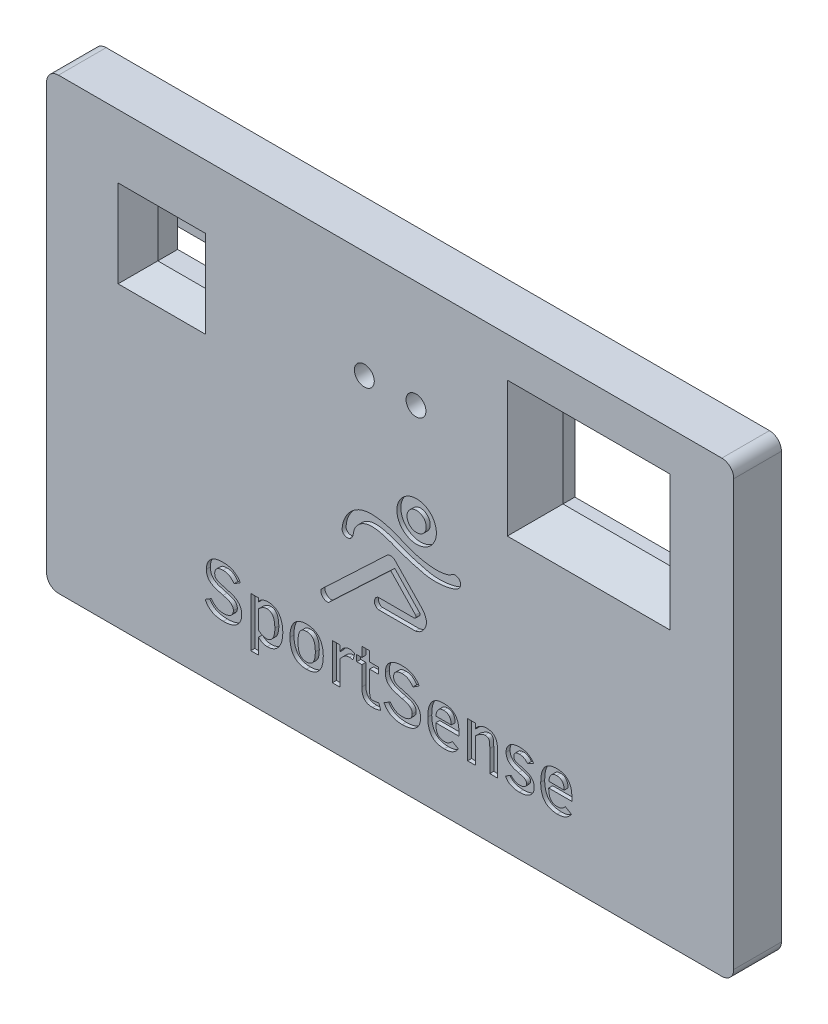
SolidWorks part; units mm, degrees
note: The reader was unsure of these and kept them because the rebuilt part matched: shared geometry of "Schizzo1<5>", "Schizzo1<6>".
ref_plane "Piano frontale" through (0, 0, 0) normal (0, 0, 1) x (1, 0, 0)
ref_plane "Piano superiore" through (0, 0, 0) normal (0, 1, 0) x (1, 0, 0)
ref_plane "Piano destro" through (0, 0, 0) normal (1, 0, 0) x (0, 0, -1)
sketch "Schizzo1" plane through (0, 0, 0) normal (0, 0, 1) x (1, 0, 0)
  line L0 (68.2126, 15.5532) -> (68.2126, -4.4468)
  line L1 (-51.7874, 32.5532) -> (115.2126, 32.5532)
  line L2 (-54.7874, 29.5532) -> (-54.7874, -77.4468)
  line L3 (-51.7874, -80.4468) -> (115.2126, -80.4468)
  line L4 (118.2126, 29.5532) -> (118.2126, -77.4468)
  line L5 (68.2126, -4.4468) -> (95.2126, -4.4468)
  line L6 (95.2126, -4.4468) -> (95.2126, 15.5532)
  line L7 (95.2126, 15.5532) -> (68.2126, 15.5532)
  line L9 (-31.7874, 11.5532) -> (-19.7874, 11.5532)
  line L10 (-31.7874, 11.5532) -> (-31.7874, -0.4468)
  line L11 (-31.7874, -0.4468) -> (-19.7874, -0.4468)
  line L12 (-19.7874, 11.5532) -> (-19.7874, -0.4468)
  line L20 (-48.7874, 29.5532) -> (112.2126, 29.5532)
  line L21 (115.2126, 26.5532) -> (115.2126, -74.4468)
  line L22 (112.2126, -77.4468) -> (-48.7874, -77.4468)
  line L23 (-51.7874, -74.4468) -> (-51.7874, 26.5532)
  line L24 (59.1414, 281.4902) -> (400.4747, 281.4902) construction
  line L25 (14.2126, -15.0537) -> (49.2126, -15.0537) construction
  line L27 (49.2126, -15.0537) -> (49.2126, -50.0537) construction
  line L28 (49.2126, -50.0537) -> (14.2126, -50.0537) construction
  line L29 (14.2126, -50.0537) -> (14.2126, -15.0537) construction
  line L30 (27.7126, 5.5532) -> (35.7126, 5.5532) construction
  line L36 (-51.7874, 26.5532) -> (-48.7874, 26.5532)
  line L37 (-48.7874, 26.5532) -> (-48.7874, 29.5532)
  line L38 (112.2126, 29.5532) -> (112.2126, 26.5532)
  line L39 (112.2126, 26.5532) -> (115.2126, 26.5532)
  line L40 (112.2126, -77.4468) -> (112.2126, -74.4468)
  line L41 (112.2126, -74.4468) -> (115.2126, -74.4468)
  line L42 (-51.7874, -74.4468) -> (-48.7874, -74.4468)
  line L43 (-48.7874, -74.4468) -> (-48.7874, -77.4468)
  line L44 (32.9376, -30.8997) -> (39.574, -37.7908)
  line L46 (38.0965, -43.7186) -> (28.7862, -43.7186)
  line L48 (28.6696, -41.0421) -> (37.7346, -41.0421)
  line L49 (38.0965, -40.1972) -> (31.8572, -33.6504)
  line L50 (31.8572, -33.6504) -> (16.2441, -48.3913)
  line L52 (14.3162, -46.4595) -> (30.8267, -30.8502)
  circle A0 centre (38.2126, 5.5532) radius 2.5
  circle A1 centre (25.2126, 5.5532) radius 2.5
  arc A2 (-54.7874, 29.5532) -> (-51.7874, 32.5532) centre (-51.7874, 29.5532) cw
  arc A3 (115.2126, 32.5532) -> (118.2126, 29.5532) centre (115.2126, 29.5532) cw
  arc A4 (118.2126, -77.4468) -> (115.2126, -80.4468) centre (115.2126, -77.4468) cw
  arc A5 (-54.7874, -77.4468) -> (-51.7874, -80.4468) centre (-51.7874, -77.4468) ccw
  circle A10 centre (38.3751, -19.6964) radius 4.9713
  circle A11 centre (38.3751, -19.6964) radius 2.4232
  arc A12 (32.9376, -30.8997) -> (30.8267, -30.8502) centre (31.8572, -31.9402) ccw
  arc A14 (37.7346, -41.0421) -> (38.0965, -40.1972) centre (37.7346, -40.5421) ccw
  spline S0 degree 3 poles (14.3162, -46.4595) (13.9891, -47.5326) (15.166, -48.7606) (16.2441, -48.3913) knots 0 0 0 0 1 1 1 1
  spline S1 degree 3 poles (28.6696, -41.0421) (28.2835, -41.1794) (27.7735, -41.6833) (27.817, -42.4031) (27.7509, -42.8713) (28.1259, -43.3785) (28.4503, -43.7585) (28.7862, -43.7186) knots 0 0 0 0 0.363254 0.491066 0.604087 0.746087 1 1 1 1
  spline S2 degree 3 poles (19.793, -31.4015) (20.2216, -31.8223) (20.8676, -31.9921) (21.7255, -31.8696) (22.4091, -30.8969) (22.4939, -29.5051) (23.2553, -28.0379) (24.4564, -27.0519) (25.7745, -26.4907) (27.4515, -26.3164) (29.578, -26.6763) (31.9571, -27.4618) (34.9498, -28.7187) (38.1338, -29.6274) (41.7214, -30.5302) (44.7722, -30.4459) (47.3512, -29.9194) (49.3212, -29.061) (49.4444, -27.7859) (49.3203, -27.0451) (48.7265, -26.6227) (48.0584, -26.4969) (47.4151, -26.6189) (46.944, -27.099) (46.0503, -27.4579) (44.9375, -27.6917) (43.6653, -27.7887) (40.5421, -27.7019) (36.6571, -26.6644) (32.1528, -24.5114) (28.7992, -23.7588) (25.5477, -23.6871) (22.9138, -24.64) (20.5142, -27.034) (19.6441, -29.3787) (19.6087, -31.0181) (19.793, -31.4015) (20.2216, -31.8223) (20.8676, -31.9921) knots -0.017038 -0.01547 -0.00674 0 0.0098 0.020745 0.034916 0.056066 0.080028 0.103061 0.12129 0.140595 0.174332 0.212673 0.247713 0.313116 0.354081 0.405938 0.43994 0.471764 0.483395 0.492165 0.502628 0.51184 0.521126 0.529102 0.539884 0.561685 0.577685 0.59435 0.695262 0.746002 0.808029 0.840487 0.884323 0.923245 0.982962 0.98453 0.99326 1 1.0098 1.020745 1.034916 only from (20.1877, -31.7426) to (20.1877, -31.7426)
  spline S3 degree 3 poles (38.0965, -43.7186) (38.5055, -43.6308) (39.3147, -43.3558) (40.4674, -42.1737) (41.0463, -40.6417) (40.6345, -39.4032) (40.2889, -38.5798) (39.7917, -38.1268) (39.574, -37.7908) knots 0 0 0 0 0.167537 0.327367 0.648773 0.740515 0.840902 1 1 1 1
  point P18 (-54.7874, 32.5532)
  point P21 (118.2126, 32.5532)
  point P24 (118.2126, -80.4468)
  point P29 (68.2126, 5.5532)
  point P36 (-19.7874, 5.5532)
  point P49 (31.7126, 5.5532)
  point P61 (31.7126, -15.0537)
  point P80 (31.7126, 29.5532)
  dimension "D5" = 5
  dimension "D6" = 3
  dimension "D7" = 20
  dimension "D8" = 20
  dimension "D10" = 13
  dimension "D11" = 14
  dimension "D12" = 12
  dimension "D14" = 35
  dimension "D15" = 3
  dimension "D1" = 173
  dimension "D2" = 113
  dimension "D3" = 27
  dimension "D4" = 20
extrude "Bordo" add sketch "Schizzo1" against normal blind 2
extrude "Coperchio" add sketch "Schizzo1<5>" along normal blind 10
sketch "Schizzo1<5>" plane through (0, 0, 0) normal (0, 0, 1) x (1, 0, 0) same geometry as "Schizzo1"
extrude "Logo" add sketch "Schizzo1<6>" along normal blind 9 contours A10 A11 | S2 | L46 S3 L44 A12 L52 S0 L50 L49 A14 L48 S1
sketch "Schizzo1<6>" plane through (0, 0, 0) normal (0, 0, 1) x (1, 0, 0) same geometry as "Schizzo1"
sketch "Schizzo2" plane through (0, 0, 10) normal (0, 0, 1) x (1, 0, 0)
  line L0 (79.1261, -65.4468) -> (-15.7009, -65.4468) construction
  line L5 (-51.7874, -80.4468) -> (115.2126, -80.4468) construction
  line L7 (-51.7874, -80.4468) -> (115.2126, -80.4468) construction
  text T0 "<b>SportSense</b>\r\n" font "Clear Sans" height 12
  point P2 (31.7126, -80.4468)
  point P3 (0, 0)
  point P4 (0, 0)
  point P5 (0, 0)
  point P7 (45.3559, -65.4468)
  point P8 (-27.9161, -65.4468)
  point P9 (69.057, -65.4468)
  point P10 (75.0984, -65.4468)
  point P13 (39.7722, -62.6905)
  point P14 (79.1261, -65.4468)
  point P15 (33.3048, -62.9604)
  point P16 (0, 0)
  point P18 (31.7126, -65.4468)
  dimension "D1" = 15
extrude "Nome" cut sketch "Schizzo2" against normal blind 1
chamfer "Smusso3" distance 7 angle 45 4 edges at (95.2126, 5.5532, 10) (81.7126, -4.4468, 10) (68.2126, 5.5532, 10) (81.7126, 15.5532, 10)
chamfer "Smusso4" distance 5 angle 45 4 edges at (-31.7874, 5.5532, 10) (-25.7874, -0.4468, 10) (-19.7874, 5.5532, 10) (-25.7874, 11.5532, 10)
sketch "Schizzo7" plane through (0, 0, 0) normal (0, 0, -1) x (-1, 0, 0)
  line L0 (31.7874, 4.5532) -> (33.7874, 4.5532)
  line L1 (31.7874, 11.5532) -> (31.7874, -0.4468) construction
  line L2 (33.7874, 4.5532) -> (33.7874, 6.5532)
  line L3 (33.7874, 6.5532) -> (31.7874, 6.5532)
  line L4 (31.7874, 6.5532) -> (31.7874, 4.5532)
  line L5 (19.7874, 4.5532) -> (17.7874, 4.5532)
  line L6 (19.7874, 11.5532) -> (19.7874, -0.4468) construction
  line L7 (17.7874, 4.5532) -> (17.7874, 6.5532)
  line L8 (17.7874, 6.5532) -> (19.7874, 6.5532)
  line L9 (19.7874, 6.5532) -> (19.7874, 4.5532)
  line L10 (19.7874, 11.5532) -> (19.7874, -0.4468)
  point P14 (19.7874, 5.5532)
  point P15 (19.7874, 5.5532)
  point P16 (31.7874, 5.5532)
  line M6 (31.7874, 11.5532) -> (31.7874, -0.4468)
  line M8 (19.7874, -0.4468) -> (19.7874, 11.5532)
  dimension "D1" = 2
  dimension "D2" = 2
extrude "Aggancio Tasto 1" add sketch "Schizzo7" along normal blind 2 contours L8 L7 L5 M8 | L2 L3 L0 M6
sketch "Schizzo8" plane through (-19.7874, 0, 0) normal (-1, 0, 0) x (0, 0, 1)
  line L0 (-2, 6.5532) -> (-2, 4.5532)
  line L2 (0, 4.5532) -> (0, 6.5532)
  line L3 (0, 6.5532) -> (-2, 6.5532)
  line L4 (-2, 4.5532) -> (-2, 6.5532) construction
  line L5 (-2, 4.5532) -> (0, 4.5532)
extrude "Aggancio Tasto 2" add sketch "Schizzo8" along normal up to surface (12 mm away) up to face at (-31.7874, 5.5532, 0.75)
chamfer "Smusso5" distance 2 angle 45 2 edges at (-17.7874, 5.5532, -2) (-33.7874, 5.5532, -2)
